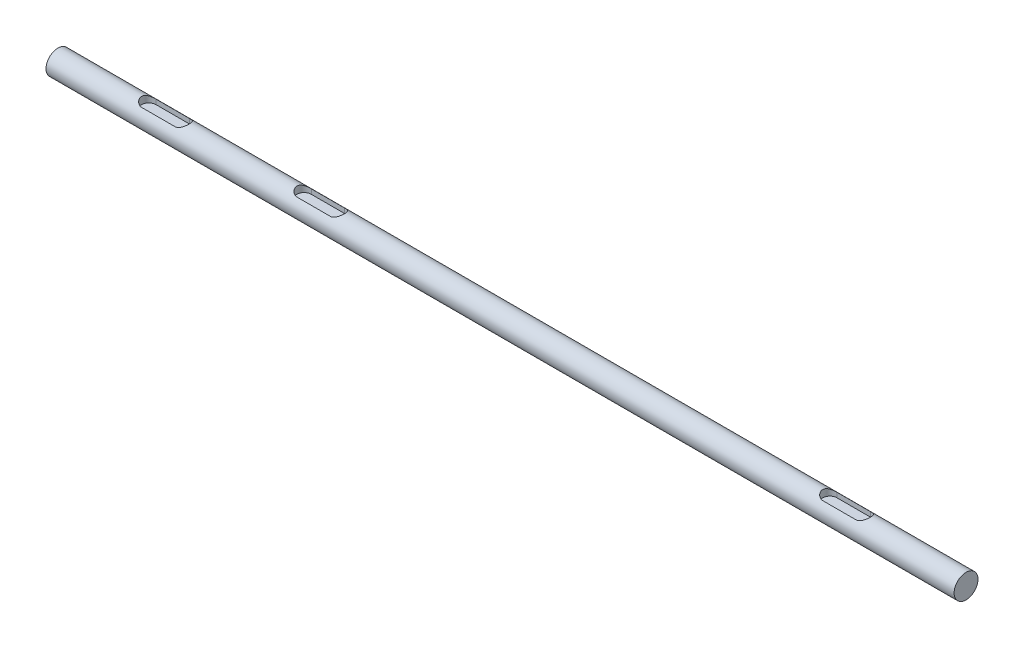
SolidWorks part; units mm, degrees
material "45"
ref_plane "前视基准面" through (0, 0, 0) normal (0, 0, 1) x (1, 0, 0)
ref_plane "上视基准面" through (0, 0, 0) normal (0, 1, 0) x (1, 0, 0)
ref_plane "右视基准面" through (0, 0, 0) normal (1, 0, 0) x (0, 0, -1)
ref_axis "基准轴1" through (88.99, 0, 0) along (-1, 0, 0)
sketch "草图1" plane through (0, 0, 0) normal (1, 0, 0) x (0, 0, -1)
  circle A0 centre (0, 0) radius 5
extrude "凸台-拉伸1" add sketch "草图1" along normal blind 150
ref_plane "基准面1" through (0, 5, 0) normal (0, 1, 0) x (1, 0, 0)
sketch "草图2" plane through (0, 5, 0) normal (0, 1, 0) x (1, 0, 0)
  line L0 (23, 3) -> (37, 3)
  line L1 (23, -3) -> (37, -3)
  arc A0 (23, 3) -> (23, -3) centre (23, 0) ccw
  arc A1 (37, 3) -> (37, -3) centre (37, 0) cw
  dimension "D1" = 3
  dimension "D2" = 14
extrude "切除-拉伸1" cut sketch "草图2" against normal blind 3
sketch "草图3" plane through (150, 0, 0) normal (1, 0, 0) x (0, 0, -1)
  circle A0 centre (0, 0) radius 5
extrude "凸台-拉伸2" add sketch "草图3" along normal blind 150
ref_plane "基准面2" through (0, 5, 0) normal (0, 1, 0) x (1, 0, 0)
sketch "草图4" plane through (0, 5, 0) normal (0, 1, 0) x (1, 0, 0)
  line L0 (243, 3) -> (257, 3)
  line L1 (243, -3) -> (257, -3)
  arc A0 (243, 3) -> (243, -3) centre (243, 0) ccw
  arc A1 (257, 3) -> (257, -3) centre (257, 0) cw
  dimension "D1" = 3
  dimension "D2" = 14
extrude "切除-拉伸2" cut sketch "草图4" against normal blind 3
sketch "草图5" plane through (0, 0, 0) normal (-1, 0, 0) x (0, 0, 1)
  circle A0 centre (0, 0) radius 5
  dimension "D1" = 10
extrude "凸台-拉伸4" add sketch "草图5" along normal blind 80
pattern_linear "阵列(线性)2" count 2 spacing 65 along (-1, 0, 0) of "切除-拉伸1"
